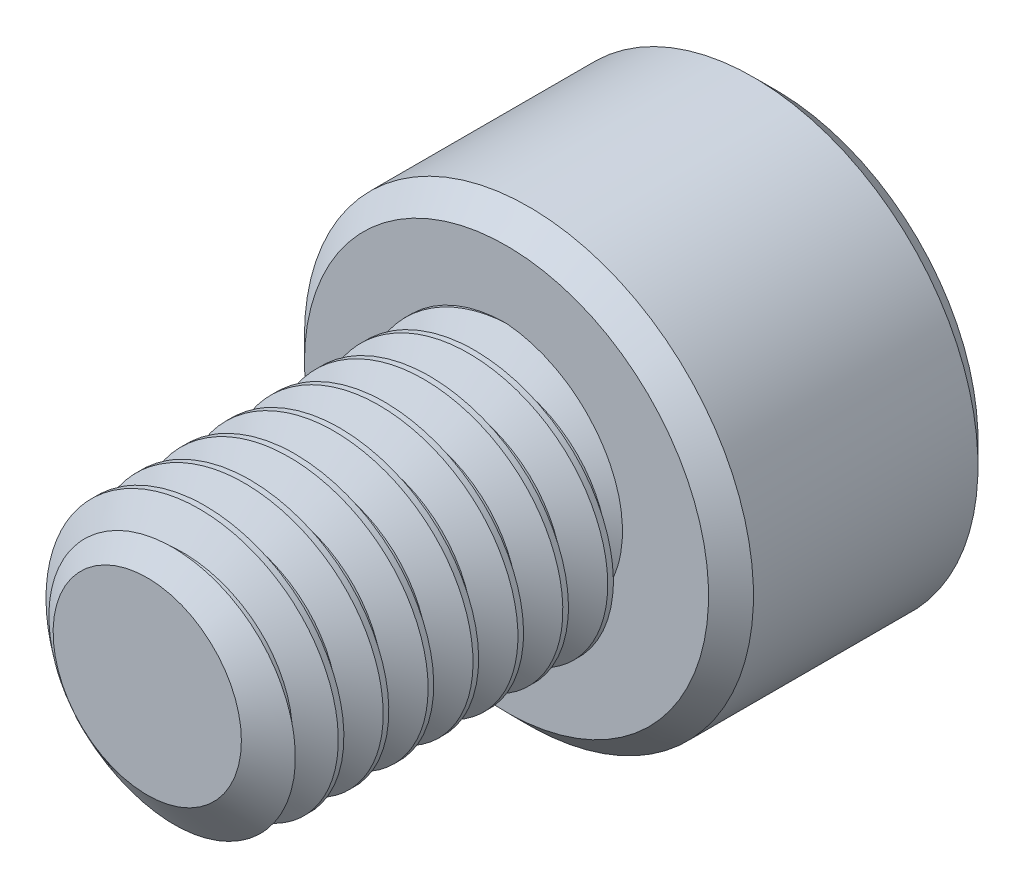
SolidWorks part; units mm, degrees
note: '?' marks a value the reader was unsure of.
other "DetailItem1"
ref_plane "Front Plane" through (0, 0, 0) normal (0, 0, 1) x (1, 0, 0)
ref_plane "Top Plane" through (0, 0, 0) normal (0, 1, 0) x (1, 0, 0)
ref_plane "Right Plane" through (0, 0, 0) normal (1, 0, 0) x (0, 0, -1)
sketch "Sketch1" plane through (0, 0, 0) normal (0, 0, 1) x (1, 0, 0)
  circle A0 centre (0, 0) radius 3
  dimension "OD" = 6
extrude "Extrude1" add sketch "Sketch1" against normal blind 8
sketch "Sketch2" plane through (0, 0, 0) normal (0, 0, 1) x (1, 0, 0)
  circle A0 centre (0, 0) radius 3 construction
  circle A1 centre (0, 0) radius 3
curve "Helix/Spiral1" pitch 1 height 9 turns 9 parameters "pitch"=1
sketch "Sketch3" plane through (0, 0, 0) normal (1, 0, 0) x (0, 0, -1)
  line L0 (-0.875, 3) -> (-0.5, 2.3505)
  line L1 (-0.5, 2.3505) -> (-0.375, 2.3505)
  line L2 (-0.375, 2.3505) -> (0, 3)
  line L3 (-0.875, 3) -> (0, 3)
  line L4 (-0.4375, 3) -> (-0.4375, 2.3505) construction
  line L5 (-0.6875, 2.6752) -> (-0.1875, 2.6752) construction
  line L6 (0, 3) -> (0, -3) construction
  dimension "D1" = 0.125
  dimension "D2" = 0.5
  dimension "D3" = 60
sweep "Cut-Sweep1" cut profiles "Sketch3" path "Helix/Spiral1"
sketch "Sketch4" plane through (0, 0, 0) normal (1, 0, 0) x (0, 0, -1)
  line L0 (0.6327, 3) -> (0, 2.0965)
  line L1 (0, 2.0965) -> (0, 3)
  line L2 (0.6327, 3) -> (0, 3)
  line L3 (-0.875, 3) -> (0, 3) construction
  line L4 (0, 0) -> (7.0209, 0) construction
  dimension "D1" = 55
  dimension "D2" = 0.254
revolve "Cut-Revolve1" cut sketch "Sketch4" angle 360 about L4
sketch "Sketch6" plane through (0, 0, -8) normal (0, 0, -1) x (-1, 0, 0)
  circle A0 centre (0, 0) radius 5
  dimension "head dia" = 10
extrude "Extrude2" add sketch "Sketch6" along normal blind 6
sketch "Sketch7" plane through (0, 0, -14) normal (0, 0, -1) x (-1, 0, 0)
  line L1 (0, 2.8868) -> (-2.5, 1.4434)
  line L2 (-2.5, 1.4434) -> (-2.5, -1.4434)
  line L3 (-2.5, -1.4434) -> (0, -2.8868)
  line L4 (0, -2.8868) -> (2.5, -1.4434)
  line L5 (2.5, -1.4434) -> (2.5, 1.4434)
  line L6 (2.5, 1.4434) -> (0, 2.8868)
  circle A0 centre (0, 0) radius 2.5 construction
  dimension "hex dia" = 5
extrude "Cut-Extrude1" cut sketch "Sketch7" against normal blind 3.75
sketch "Sketch8" plane through (0, 0, -14) normal (0, 0, -1) x (-1, 0, 0)
  circle A0 centre (0, 0) radius 2.8868
extrude "Cut-Extrude2" cut sketch "Sketch8" against normal through all draft 45
chamfer "Chamfer1" distance 0.5 angle 45 2 edges at (-5, 0, -14) (-5, 0, -8)
sketch "Sketch10" plane through (0, 0, -8) normal (0, 0, 1) x (1, 0, 0)
  circle A1 centre (0, 0) radius 3
  circle A2 centre (0, 0) radius 3
  dimension "D1" = 0
ref_plane "Plane1" through (0, 0, 0) normal (0, 0, 1) x (1, 0, 0)
extrude "partial thread" [suppressed] add sketch "Sketch10" along normal up to surface (31 mm away) separate body
chamfer "Chamfer2" [suppressed] distance 0.12 angle 45
combine bodies "Combine1" [suppressed] operation type? add bodies to combine 107 108
sketch "Sketch9" plane through (0, 0, 0) normal (1, 0, 0) x (0, 0, -1)
  line L0 (0, 3) -> (0, -3) construction
  line L1 (2.5, 3) -> (2.5, -3) construction
  dimension "D1" = 2.5
equation "\"D3@Helix/Spiral1\" = \"screw length@Extrude1\"+\"pitch@Helix/Spiral1\""
equation "\"D1@Sketch3\" = \"pitch@Helix/Spiral1\"*.125"
equation "\"D2@Sketch3\" = \"pitch@Helix/Spiral1\"*.5"
equation "\"D1@Cut-Extrude1\" = \"hex dia@Sketch7\"*.75"
equation "\"D1@Chamfer1\" = \"head dia@Sketch6\"*.05"
equation "\"D1@Sketch9\" = \"pitch@Helix/Spiral1\"*2.5"
equation "\"D1@Chamfer2\"=\"OD@Sketch1\"*.02"
